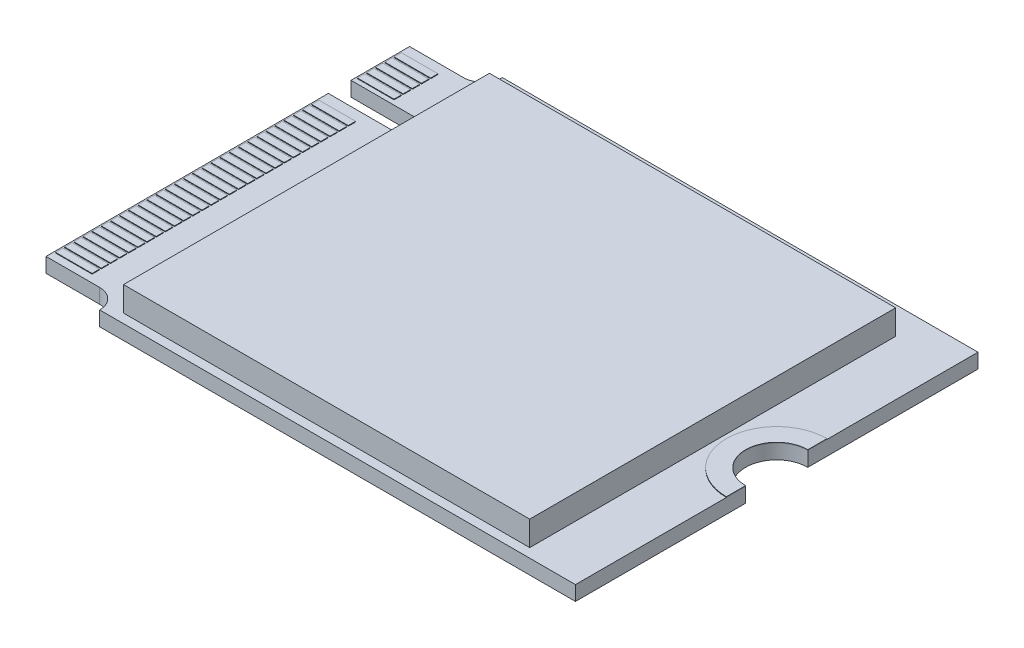
SolidWorks part; units mm, degrees
ref_plane "Front Plane" through (0, 0, 0) normal (0, 0, 1) x (1, 0, 0)
ref_plane "Top Plane" through (0, 0, 0) normal (0, 1, 0) x (1, 0, 0)
ref_plane "Right Plane" through (0, 0, 0) normal (1, 0, 0) x (0, 0, -1)
sketch "Sketch1" plane through (0, 0, 0) normal (0, 1, 0) x (1, 0, 0)
  line L0 (0, 0) -> (18017.9839, 0) construction
  line L1 (-15, 0) -> (-15, 5.495)
  line L2 (-15, 5.495) -> (-11.6, 5.495)
  line L3 (-11.6, 6.735) -> (-15, 6.735)
  line L4 (-15, 6.735) -> (-15, 9.935)
  line L5 (-15, 9.935) -> (-12.065, 9.935)
  line L6 (-11, 11) -> (0, 11)
  line L7 (-15, -9.935) -> (-12.065, -9.935)
  line L8 (0, 11) -> (15, 11)
  line L11 (15, -11) -> (-11, -11)
  line L12 (-15, -9.935) -> (-15, 0)
  line L13 (-11, 11) -> (-11, -11) construction
  line L14 (15, 11) -> (15, 1.7)
  line L15 (15, -11) -> (15, -1.7)
  arc A0 (-11.6, 5.495) -> (-11.6, 6.735) centre (-11.6, 6.115) ccw
  arc A3 (-12.065, 9.935) -> (-11, 11) centre (-12.065, 11) ccw
  arc A4 (-12.065, -9.935) -> (-11, -11) centre (-12.065, -11) cw
  arc A5 (15, 1.7) -> (15, -1.7) centre (15, 0) ccw
  point P22 (13.3, 0)
  dimension "D5" = 30
  dimension "D8" = 28.3
  dimension "D9" = 26.6
  dimension "D1" = 3.2
  dimension "D2" = 15.43
  dimension "D3" = 22
  dimension "D4" = 15
  dimension "D6" = 26
  dimension "D7" = 19.87
extrude "Boss-Extrude1" add sketch "Sketch1" along normal blind 0.8
sketch "Sketch2" plane through (0, 0.8, 0) normal (0, 1, 0) x (1, 0, 0)
  line L0 (-15, 9.935) -> (-15, 6.735) construction
  line L1 (-14.9, 8.985) -> (-12.9, 8.985)
  line L2 (-14.9, 8.985) -> (-14.9, 9.385)
  line L3 (-14.9, 9.385) -> (-12.9, 9.385)
  line L4 (-12.9, 8.985) -> (-12.9, 9.385)
  line L5 (-14.9, 8.885) -> (-12.9, 8.885)
  line L6 (-12.9, 8.485) -> (-12.9, 8.885)
  line L7 (-14.9, 8.485) -> (-12.9, 8.485)
  line L8 (-14.9, 8.485) -> (-14.9, 8.885)
  line L9 (-14.9, 8.385) -> (-12.9, 8.385)
  line L10 (-12.9, 7.985) -> (-12.9, 8.385)
  line L11 (-14.9, 7.985) -> (-12.9, 7.985)
  line L12 (-14.9, 7.985) -> (-14.9, 8.385)
  line L13 (-14.9, 7.885) -> (-12.9, 7.885)
  line L14 (-12.9, 7.485) -> (-12.9, 7.885)
  line L15 (-14.9, 7.485) -> (-12.9, 7.485)
  line L16 (-14.9, 7.485) -> (-14.9, 7.885)
  line L17 (-14.9, 4.885) -> (-12.9, 4.885)
  line L18 (-14.9, 4.885) -> (-14.9, 4.485)
  line L19 (-14.9, 4.485) -> (-12.9, 4.485)
  line L20 (-12.9, 4.885) -> (-12.9, 4.485)
  line L21 (-14.9, 3.985) -> (-12.9, 3.985)
  line L22 (-12.9, 4.385) -> (-12.9, 3.985)
  line L23 (-14.9, 4.385) -> (-12.9, 4.385)
  line L24 (-14.9, 4.385) -> (-14.9, 3.985)
  line L25 (-14.9, 3.485) -> (-12.9, 3.485)
  line L26 (-12.9, 3.885) -> (-12.9, 3.485)
  line L27 (-14.9, 3.885) -> (-12.9, 3.885)
  line L28 (-14.9, 3.885) -> (-14.9, 3.485)
  line L29 (-14.9, 2.985) -> (-12.9, 2.985)
  line L30 (-12.9, 3.385) -> (-12.9, 2.985)
  line L31 (-14.9, 3.385) -> (-12.9, 3.385)
  line L32 (-14.9, 3.385) -> (-14.9, 2.985)
  line L33 (-14.9, 2.485) -> (-12.9, 2.485)
  line L34 (-12.9, 2.885) -> (-12.9, 2.485)
  line L35 (-14.9, 2.885) -> (-12.9, 2.885)
  line L36 (-14.9, 2.885) -> (-14.9, 2.485)
  line L37 (-14.9, 1.985) -> (-12.9, 1.985)
  line L38 (-12.9, 2.385) -> (-12.9, 1.985)
  line L39 (-14.9, 2.385) -> (-12.9, 2.385)
  line L40 (-14.9, 2.385) -> (-14.9, 1.985)
  line L41 (-14.9, 1.485) -> (-12.9, 1.485)
  line L42 (-12.9, 1.885) -> (-12.9, 1.485)
  line L43 (-14.9, 1.885) -> (-12.9, 1.885)
  line L44 (-14.9, 1.885) -> (-14.9, 1.485)
  line L45 (-14.9, 0.985) -> (-12.9, 0.985)
  line L46 (-12.9, 1.385) -> (-12.9, 0.985)
  line L47 (-14.9, 1.385) -> (-12.9, 1.385)
  line L48 (-14.9, 1.385) -> (-14.9, 0.985)
  line L49 (-14.9, 0.485) -> (-12.9, 0.485)
  line L50 (-12.9, 0.885) -> (-12.9, 0.485)
  line L51 (-14.9, 0.885) -> (-12.9, 0.885)
  line L52 (-14.9, 0.885) -> (-14.9, 0.485)
  line L53 (-14.9, -0.015) -> (-12.9, -0.015)
  line L54 (-12.9, 0.385) -> (-12.9, -0.015)
  line L55 (-14.9, 0.385) -> (-12.9, 0.385)
  line L56 (-14.9, 0.385) -> (-14.9, -0.015)
  line L57 (-14.9, -0.515) -> (-12.9, -0.515)
  line L58 (-12.9, -0.115) -> (-12.9, -0.515)
  line L59 (-14.9, -0.115) -> (-12.9, -0.115)
  line L60 (-14.9, -0.115) -> (-14.9, -0.515)
  line L61 (-14.9, -1.015) -> (-12.9, -1.015)
  line L62 (-12.9, -0.615) -> (-12.9, -1.015)
  line L63 (-14.9, -0.615) -> (-12.9, -0.615)
  line L64 (-14.9, -0.615) -> (-14.9, -1.015)
  line L65 (-14.9, -1.515) -> (-12.9, -1.515)
  line L66 (-12.9, -1.115) -> (-12.9, -1.515)
  line L67 (-14.9, -1.115) -> (-12.9, -1.115)
  line L68 (-14.9, -1.115) -> (-14.9, -1.515)
  line L69 (-14.9, -2.015) -> (-12.9, -2.015)
  line L70 (-12.9, -1.615) -> (-12.9, -2.015)
  line L71 (-14.9, -1.615) -> (-12.9, -1.615)
  line L72 (-14.9, -1.615) -> (-14.9, -2.015)
  line L73 (-14.9, -2.515) -> (-12.9, -2.515)
  line L74 (-12.9, -2.115) -> (-12.9, -2.515)
  line L75 (-14.9, -2.115) -> (-12.9, -2.115)
  line L76 (-14.9, -2.115) -> (-14.9, -2.515)
  line L77 (-14.9, -3.015) -> (-12.9, -3.015)
  line L78 (-12.9, -2.615) -> (-12.9, -3.015)
  line L79 (-14.9, -2.615) -> (-12.9, -2.615)
  line L80 (-14.9, -2.615) -> (-14.9, -3.015)
  line L81 (-14.9, -3.515) -> (-12.9, -3.515)
  line L82 (-12.9, -3.115) -> (-12.9, -3.515)
  line L83 (-14.9, -3.115) -> (-12.9, -3.115)
  line L84 (-14.9, -3.115) -> (-14.9, -3.515)
  line L85 (-14.9, -4.015) -> (-12.9, -4.015)
  line L86 (-12.9, -3.615) -> (-12.9, -4.015)
  line L87 (-14.9, -3.615) -> (-12.9, -3.615)
  line L88 (-14.9, -3.615) -> (-14.9, -4.015)
  line L89 (-14.9, -4.515) -> (-12.9, -4.515)
  line L90 (-12.9, -4.115) -> (-12.9, -4.515)
  line L91 (-14.9, -4.115) -> (-12.9, -4.115)
  line L92 (-14.9, -4.115) -> (-14.9, -4.515)
  line L93 (-14.9, -5.015) -> (-12.9, -5.015)
  line L94 (-12.9, -4.615) -> (-12.9, -5.015)
  line L95 (-14.9, -4.615) -> (-12.9, -4.615)
  line L96 (-14.9, -4.615) -> (-14.9, -5.015)
  line L97 (-14.9, -5.515) -> (-12.9, -5.515)
  line L98 (-12.9, -5.115) -> (-12.9, -5.515)
  line L99 (-14.9, -5.115) -> (-12.9, -5.115)
  line L100 (-14.9, -5.115) -> (-14.9, -5.515)
  line L101 (-14.9, -6.015) -> (-12.9, -6.015)
  line L102 (-12.9, -5.615) -> (-12.9, -6.015)
  line L103 (-14.9, -5.615) -> (-12.9, -5.615)
  line L104 (-14.9, -5.615) -> (-14.9, -6.015)
  line L105 (-14.9, -6.515) -> (-12.9, -6.515)
  line L106 (-12.9, -6.115) -> (-12.9, -6.515)
  line L107 (-14.9, -6.115) -> (-12.9, -6.115)
  line L108 (-14.9, -6.115) -> (-14.9, -6.515)
  line L109 (-14.9, -7.015) -> (-12.9, -7.015)
  line L110 (-12.9, -6.615) -> (-12.9, -7.015)
  line L111 (-14.9, -6.615) -> (-12.9, -6.615)
  line L112 (-14.9, -6.615) -> (-14.9, -7.015)
  line L113 (-14.9, -7.515) -> (-12.9, -7.515)
  line L114 (-12.9, -7.115) -> (-12.9, -7.515)
  line L115 (-14.9, -7.115) -> (-12.9, -7.115)
  line L116 (-14.9, -7.115) -> (-14.9, -7.515)
  line L117 (-14.9, -8.015) -> (-12.9, -8.015)
  line L118 (-12.9, -7.615) -> (-12.9, -8.015)
  line L119 (-14.9, -7.615) -> (-12.9, -7.615)
  line L120 (-14.9, -7.615) -> (-14.9, -8.015)
  line L121 (-14.9, -8.515) -> (-12.9, -8.515)
  line L122 (-12.9, -8.115) -> (-12.9, -8.515)
  line L123 (-14.9, -8.115) -> (-12.9, -8.115)
  line L124 (-14.9, -8.115) -> (-14.9, -8.515)
  line L125 (-14.9, -9.015) -> (-12.9, -9.015)
  line L126 (-12.9, -8.615) -> (-12.9, -9.015)
  line L127 (-14.9, -8.615) -> (-12.9, -8.615)
  line L128 (-14.9, -8.615) -> (-14.9, -9.015)
  line L129 (-14.9, -9.515) -> (-12.9, -9.515)
  line L130 (-12.9, -9.115) -> (-12.9, -9.515)
  line L131 (-14.9, -9.115) -> (-12.9, -9.115)
  line L132 (-14.9, -9.115) -> (-14.9, -9.515)
  line L133 (-13.9, 6.985) -> (-13.9, 4.885) construction
  line L134 (-14.9, 6.985) -> (-12.9, 6.985)
  line L135 (-15, 6.735) -> (-11.6, 6.735) construction
  line L136 (-12.9, 6.985) -> (-12.9, 7.385)
  line L137 (-14.9, 7.385) -> (-12.9, 7.385)
  line L138 (-14.9, 6.985) -> (-14.9, 7.385)
  line L139 (15, -1.7) -> (15, 1.7) construction
  line L144 (15, 1.7) -> (15, 2.75)
  line L145 (15, -2.75) -> (15, -1.7)
  arc A0 (15, -1.7) -> (15, 1.7) centre (15, 0) cw
  arc A3 (15, -2.75) -> (15, 2.75) centre (15, 0) cw
  point P22 (-14.9, 7.685)
  point P135 (-14.9, 4.685)
  point P136 (-14.9, 8.185)
  point P146 (-14.9, 7.185)
  dimension "D12" = 1.7
  dimension "D13" = 2.75
  dimension "D1" = 2
  dimension "D2" = 0.1
  dimension "D3" = 0.5
  dimension "D6" = 2.5
  dimension "D7" = 0.4
  dimension "D8" = 2
  dimension "D9" = 0.5
  dimension "D10" = 0.25
  dimension "D11" = 0.5
  dimension "D4" = 4
  dimension "D5" = 29
extrude "Boss-Extrude2" add sketch "Sketch2" along normal blind 0.035 separate body
extrude "Boss-Extrude3" add sketch "Sketch2<2>" against normal blind 0.035 from offset 0.8 separate body contours L20 L17 L18 L19 | L23 L24 L21 L22 | L27 L28 L25 L26 | L31 L32 L29 L30 | L39 L40 L37 L38 | L47 L48 L45 L46 | L51 L52 L49 L50 | L55 L56 L53 L54 | L103 L104 L101 L102 | L115 L116 L113 L114 | L123 L124 L121 L122 | L127 L128 L125 L126 | L33 L34 L35 L36 | L43 L42 L41 L44 | L57 L58 L59 L60 | L61 L62 L63 L64 | L65 L66 L67 L68 | L69 L70 L71 L72 | L73 L74 L75 L76 | L77 L78 L79 L80 | L81 L82 L83 L84 | L85 L86 L87 L88 | L89 L90 L91 L92 | L93 L94 L95 L96 | L97 L98 L99 L100 | L105 L106 L107 L108 | L109 L110 L111 L112 | L119 L118 L117 L120 | L131 L130 L129 L132 region at (-13.9, 0.8, -4.685) region at (-13.9, 0.8, -4.185) region at (-13.9, 0.8, -3.685) region at (-13.9, 0.8, -3.185) region at (-13.9, 0.8, -2.185) region at (-13.9, 0.8, -1.185) region at (-13.9, 0.8, -0.685) region at (-13.9, 0.8, -0.185) region at (-13.9, 0.8, 5.815) region at (-13.9, 0.8, 7.315) region at (-13.9, 0.8, 8.315) region at (-13.9, 0.8, 8.815) offset against normal yes
sketch "Sketch2<2>" plane through (0, 0.8, 0) normal (0, 1, 0) x (1, 0, 0) same geometry as "Sketch2"
sketch "Sketch3" plane through (0, 0.8, 0) normal (0, 1, 0) x (1, 0, 0)
  line L0 (15, 1.7) -> (15, 11) construction
  line L1 (-10.2, -10.5) -> (12, -10.5)
  line L2 (-10.2, -10.5) -> (-10.2, 9.5)
  line L3 (-10.2, 9.5) -> (12, 9.5)
  line L4 (12, -10.5) -> (12, 9.5)
  line L5 (12, -0.5) -> (13.663, -0.5) construction
  line L6 (-11, -11) -> (15, -11) construction
  circle A0 centre (15, 0) radius 1.7 construction
  dimension "D1" = 20
  dimension "D2" = 22.2
  dimension "D3" = 3
  dimension "D4" = 0.5
extrude "Boss-Extrude4" add sketch "Sketch3" along normal blind 1.35
ref_plane "MID_PCB" through (0, 0.4, 0) normal (0, 1, 0) x (1, 0, 0)
sketch "Sketch4" plane through (0, 0, 0) normal (0, -1, 0) x (1, 0, 0)
  line L0 (-14.9, -4.885) -> (-14.9, -4.485) construction
  line L1 (-14.9, -7.635) -> (-12.9, -7.635)
  line L2 (-14.9, -7.635) -> (-14.9, -7.235)
  line L3 (-14.9, -7.235) -> (-12.9, -7.235)
  line L4 (-12.9, -7.635) -> (-12.9, -7.235)
  line L5 (-12.9, -4.885) -> (-12.9, -4.485) construction
  line L6 (-14.9, -8.135) -> (-12.9, -8.135)
  line L7 (-12.9, -8.135) -> (-12.9, -7.735)
  line L8 (-14.9, -7.735) -> (-12.9, -7.735)
  line L9 (-14.9, -8.135) -> (-14.9, -7.735)
  line L10 (-14.9, -8.635) -> (-12.9, -8.635)
  line L11 (-12.9, -8.635) -> (-12.9, -8.235)
  line L12 (-14.9, -8.235) -> (-12.9, -8.235)
  line L13 (-14.9, -8.635) -> (-14.9, -8.235)
  line L14 (-14.9, -9.135) -> (-12.9, -9.135)
  line L15 (-12.9, -9.135) -> (-12.9, -8.735)
  line L16 (-14.9, -8.735) -> (-12.9, -8.735)
  line L17 (-14.9, -9.135) -> (-14.9, -8.735)
  line L18 (-15.9883, -9.385) -> (-15.9883, -6.985) construction
  line L19 (-14.9, -8.235) -> (-14.9, -8.135) construction
  line L20 (-14.9, -8.185) -> (-15.9883, -8.185) construction
  line L21 (-14.9, -6.985) -> (-12.9, -6.985) construction
  line L22 (-12.9, -9.385) -> (-14.9, -9.385) construction
  point P24 (0, 0)
  point P25 (0, 0)
  point P28 (0, 0)
  point P31 (-14.9, -6.985)
  dimension "D2" = 0.5
  dimension "D1" = 4
extrude "Boss-Extrude5" add sketch "Sketch4" along normal blind 0.035 separate body
